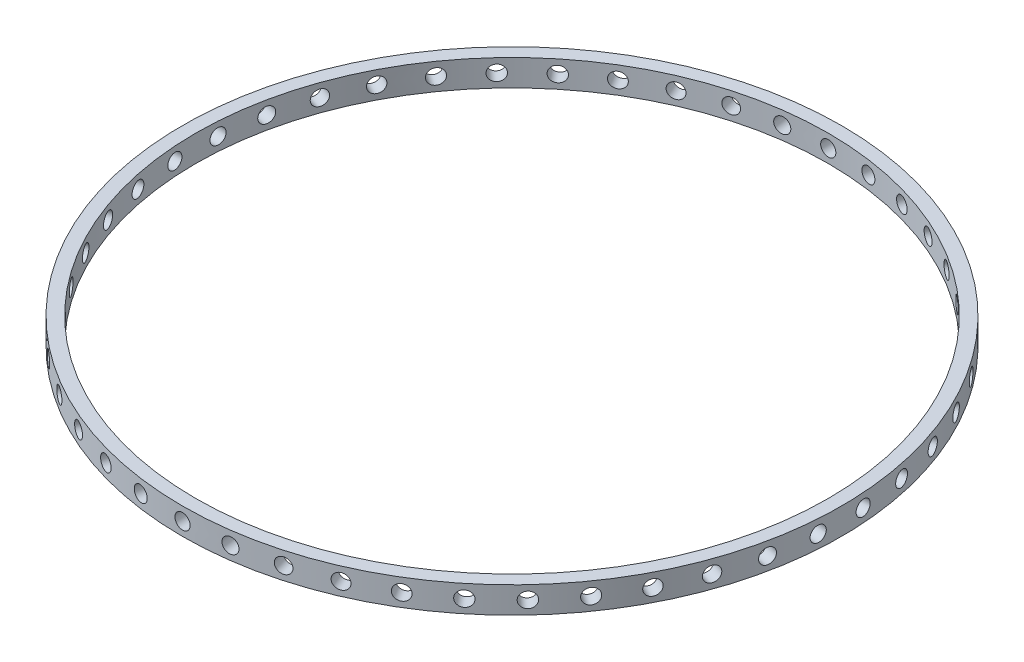
SolidWorks part; units mm, degrees
material "AISI 316 Stainless Steel Sheet (SS)"
ref_plane "Front Plane" through (0, 0, 0) normal (0, 0, 1) x (1, 0, 0)
ref_plane "Top Plane" through (0, 0, 0) normal (0, 1, 0) x (1, 0, 0)
ref_plane "Right Plane" through (0, 0, 0) normal (1, 0, 0) x (0, 0, -1)
sketch "Sketch1" plane through (0, 0, 0) normal (0, 1, 0) x (1, 0, 0)
  circle A0 centre (0, 0) radius 76.2
  circle A1 centre (0, 0) radius 79.375
  dimension "D1" = 152.4
  dimension "D2" = 3.175
extrude "Boss-Extrude1" add sketch "Sketch1" along normal blind 6.35
hole_wizard "#6 Clearance Hole2" positions "3DSketch1" profile "Sketch4" hole size "#6" standard "ANSI Inch"
sketch3d "3DSketch1"
  line L0 (0, 0, 0) -> (0, 0, 79.375) construction
  line L1 (0, 0, 79.375) -> (0, 6.35, 79.375) construction
  circle A0 centre (0, 0, 0) radius 79.375 construction
  circle A1 centre (0, 6.35, 0) radius 79.375 construction
  point P0 (0, 3.175, 79.375)
  point P8 (0, 79.375, 0)
  point P12 (0, 85.725, 0)
sketch "Sketch4" plane through (0, 3.175, 79.375) normal (1, 0, 0) x (0, -1, 0)
  line L0 (0, 0) -> (0, 13.7989)
  line L1 (0, 13.7989) -> (1.8288, 12.7)
  line L2 (1.8288, 12.7) -> (1.8288, 0)
  line L5 (1.8288, 0) -> (0, 0)
  line L10 (0, 13.7989) -> (-1.8288, 12.7) construction
  line L11 (0, -6.35) -> (0, 107.95) construction
  dimension "Hole Dia." = 3.6576
  dimension "Hole Depth" = 12.7
  dimension "Drill Angle" = 118
pattern_circular "CirPattern1" count 46 over 360 about axis through (0, 6.35, 0) along (0, -1, 0) of "#6 Clearance Hole2"
equation "\"D1@CirPattern1\"=\"blade number@[TP] [Turb] Turbine.Assembly\""
